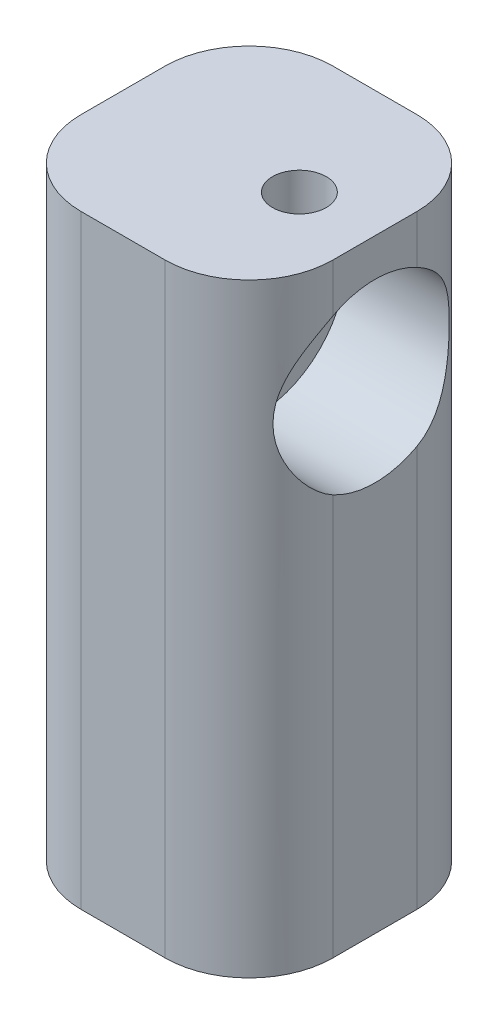
SolidWorks part; units mm, degrees
ref_plane "Front Plane" through (0, 0, 0) normal (0, 0, 1) x (1, 0, 0)
ref_plane "Top Plane" through (0, 0, 0) normal (0, 1, 0) x (1, 0, 0)
ref_plane "Right Plane" through (0, 0, 0) normal (1, 0, 0) x (0, 0, -1)
sketch "Sketch1" plane through (0, 0, 0) normal (0, 1, 0) x (1, 0, 0)
  line L1 (7.5, -7.5) -> (-7.5, -7.5)
  line L2 (7.5, -7.5) -> (7.5, 7.5)
  line L3 (7.5, 7.5) -> (-7.5, 7.5)
  line L4 (-7.5, -7.5) -> (-7.5, 7.5)
  line L5 (7.5, -7.5) -> (-7.5, 7.5) construction
  line L6 (7.5, 7.5) -> (-7.5, -7.5) construction
  circle A0 centre (0, 0) radius 4.25
  point P0 (0, 0)
  dimension "D1" = 8.5
  dimension "D2" = 15
extrude "Boss-Extrude1" add sketch "Sketch1" along normal blind 20
sketch "Sketch2" plane through (0, 20, 0) normal (0, 1, 0) x (1, 0, 0)
  line L1 (-7.5, -7.5) -> (7.5, -7.5)
  line L2 (-7.5, -7.5) -> (-7.5, 7.5)
  line L3 (-7.5, 7.5) -> (7.5, 7.5)
  line L4 (7.5, -7.5) -> (7.5, 7.5)
  line L5 (-7.5, -7.5) -> (7.5, 7.5) construction
  line L6 (-7.5, 7.5) -> (7.5, -7.5) construction
  point P0 (0, 0)
extrude "Boss-Extrude2" add sketch "Sketch2" along normal blind 16
sketch "Sketch3" plane through (7.5, 0, 0) normal (1, 0, 0) x (0, 0, -1)
  line L0 (-7.5, 36) -> (7.5, 36) construction
  circle A0 centre (0, 28.5) radius 2.5
  point P2 (0, 0)
  dimension "D2" = 5
  dimension "D1" = 7.5
extrude "Cut-Extrude1" cut sketch "Sketch3" against normal through all
fillet "Fillet1" radius 5 4 edges at (-7.5, 18, -7.5) (7.5, 18, -7.5) (-7.5, 18, 7.5) (7.5, 18, 7.5)
sketch "Sketch4" plane through (7.5, 0, 0) normal (1, 0, 0) x (0, 0, -1)
  circle A0 centre (0, 28.5) radius 5.25
  dimension "D1" = 10.5
extrude "Cut-Extrude2" cut sketch "Sketch4" against normal blind 7
sketch "Sketch5" plane through (0, 36, 0) normal (0, 1, 0) x (1, 0, 0)
  circle A0 centre (3, 0) radius 1.6
  point P2 (0, 0)
  dimension "D2" = 3.2
  dimension "D1" = 3
extrude "Cut-Extrude3" cut sketch "Sketch5" against normal up to next
chamfer "Chamfer1" distance 10 angle 1 1 edges at (0, 20, 4.25) first distance on face at (0, 20, 4.25)
